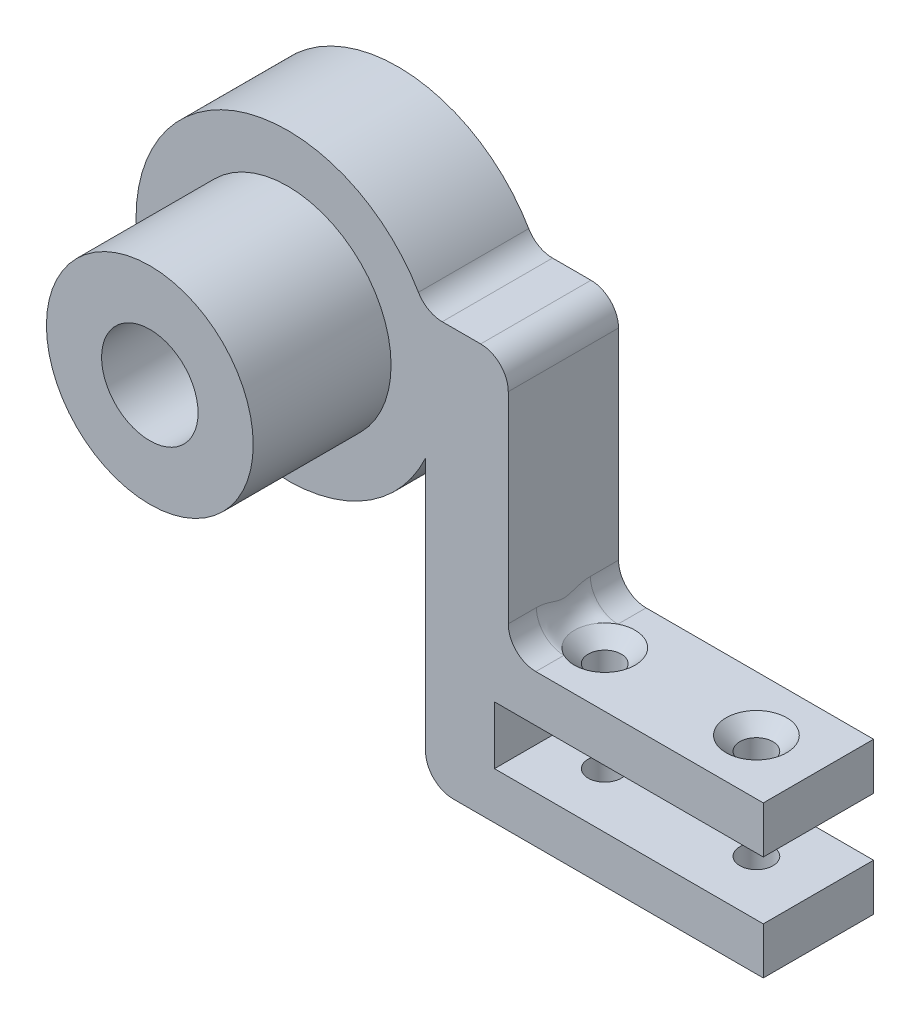
SolidWorks part; units mm, degrees
ref_plane "Plan de face" through (0, 0, 0) normal (0, 0, 1) x (1, 0, 0)
ref_plane "Plan de dessus" through (0, 0, 0) normal (0, 1, 0) x (1, 0, 0)
ref_plane "Plan de droite" through (0, 0, 0) normal (1, 0, 0) x (0, 0, -1)
sketch "Esquisse1" plane through (0, 0, 0) normal (0, 0, 1) x (1, 0, 0)
  line L1 (0, 0) -> (45.5, 0) construction
  line L2 (0, 0) -> (0, -36) construction
  line L3 (0, -36) -> (45.5, -36) construction
  line L4 (45.5, 0) -> (45.5, -36) construction
  line L5 (21, -6.4174) -> (27, -6.4174)
  line L7 (27, -6.4174) -> (27, -25)
  line L8 (45.5, -28.4) -> (45.5, -25)
  line L9 (45.5, -36) -> (21, -36)
  line L10 (45.5, -36) -> (45.5, -32.6)
  line L11 (45.5, -25) -> (27, -25)
  line L14 (21, -36) -> (21, -15.5826)
  line L17 (45.5, -32.6) -> (26, -32.6)
  line L19 (45.5, -28.4) -> (26, -28.4)
  line L20 (26, -32.6) -> (26, -28.4)
  line L21 (21, -6.4174) -> (21, -15.5826) construction
  arc A0 (21, -6.4174) -> (21, -15.5826) centre (11, -11) ccw
  point P6 (21, -11)
  point P20 (26, -30.5)
  dimension "D3" = 22
  dimension "D1" = 45.5
  dimension "D2" = 36
  dimension "D4" = 11
  dimension "D5" = 11
  dimension "D6" = 11
  dimension "D8" = 19.5
  dimension "D9" = 4.2
  dimension "D10" = 5.5
  dimension "D11" = 18.5
  dimension "D7" = 21
extrude "Boss.-Extru.1" add sketch "Esquisse1" along normal blind 8
sketch "Esquisse2" plane through (0, -25, 0) normal (0, 1, 0) x (1, 0, 0)
  line L0 (27, -8) -> (27, 0) construction
  line L1 (45.5, -8) -> (27, -8) construction
  circle A0 centre (30, -4) radius 1
  dimension "D1" = 2
  dimension "D2" = 3
  dimension "D3" = 4
extrude "Enlèv. mat.-Extru.1" cut sketch "Esquisse2" against normal up to surface (11 mm away) up to face at (33.25, -36, 4)
hole_wizard "Fraisage pour vis à tête fraisée M21" positions "Esquisse3" profile "Esquisse4" countersink size "M2" standard "ISO"
sketch "Esquisse3" plane through (0, -25, 0) normal (0, 1, 0) x (1, 0, 0)
  point P0 (30, -4)
sketch "Esquisse4" plane through (30, -25, 4) normal (1, 0, 0) x (0, 0, 1)
  line L0 (0, 0) -> (0, 11.721)
  line L1 (0, 11.721) -> (1.2, 11)
  line L2 (1.2, 11) -> (1.2, 1)
  line L3 (1.2, 1) -> (2.2, 0)
  line L5 (2.2, 0) -> (0, 0)
  line L6 (-1.2, 1) -> (-2.2, 0) construction
  line L10 (0, 11.721) -> (-1.2, 11) construction
  line L11 (0, -6.35) -> (0, 107.95) construction
  dimension "Diamètre du perçage" = 2.4
  dimension "Profondeur du perçage" = 11
  dimension "Diamètre du fraisage entrant" = 4.4
  dimension "Angle du fraisage entrant" = 90
  dimension "Angle de pointe" = 118
fillet "Congé1" radius 2 3 edges at (21, -36, 4) (21, -6.4174, 4) (27, -6.4174, 4)
sketch "Esquisse5" plane through (0, 0, 8) normal (0, 0, 1) x (1, 0, 0)
  circle A0 centre (11, -11) radius 7.5
  dimension "D1" = 15
extrude "Boss.-Extru.2" add sketch "Esquisse5" along normal blind 10
sketch "Esquisse6" plane through (0, 0, 0) normal (0, 0, -1) x (-1, 0, 0)
  line L0 (-11, -3.5) -> (-11, -18.5) construction
  line L1 (0, -4.0566) -> (0, -19.2348) construction
  line L2 (-19.6078, 0) -> (-3.8534, 0) construction
  circle A0 centre (-11, -3.5) radius 1
  circle A1 centre (-11, -18.5) radius 1
  arc A2 (-21, -15.5826) -> (-20.4856, -5.4301) centre (-11, -11) ccw construction
  circle A3 centre (-11, -11) radius 3.5 construction
  point P8 (-11, -11)
  dimension "D2" = 2
  dimension "D3" = 2
  dimension "D5" = 7
  dimension "D1" = 11
  dimension "D4" = 11
  dimension "D6" = 15
extrude "Enlèv. mat.-Extru.2" cut sketch "Esquisse6" against normal offset from surface (6 mm away) 2 up to face at (18.5, -11, 8)
sketch "Esquisse8" plane through (0, 0, 0) normal (0, 0, -1) x (-1, 0, 0)
  circle A0 centre (-11, -11) radius 3.5
  dimension "D1" = 7
extrude "Enlèv. mat.-Extru.3" cut sketch "Esquisse8" against normal up to surface (18 mm away) up to face at (18.5, -11, 18)
sketch "Esquisse9" plane through (0, -25, 0) normal (0, 1, 0) x (1, 0, 0)
  line L0 (45.5, -8) -> (27, -8) construction
  line L1 (45.5, -8) -> (45.5, 0) construction
  circle A0 centre (41, -4) radius 1
  dimension "D3" = 2
  dimension "D1" = 4
  dimension "D2" = 4.5
extrude "Enlèv. mat.-Extru.4" cut sketch "Esquisse9" against normal up to surface (11 mm away) up to face at (34.25, -36, 4)
hole_wizard "Fraisage pour vis à tête fraisée M22" positions "Esquisse10" profile "Esquisse11" countersink size "M2" standard "ISO"
sketch "Esquisse10" plane through (0, -25, 0) normal (0, 1, 0) x (1, 0, 0)
  point P0 (41, -4)
sketch "Esquisse11" plane through (41, -25, 4) normal (1, 0, 0) x (0, 0, 1)
  line L0 (0, 0) -> (0, 11.721)
  line L1 (0, 11.721) -> (1.2, 11)
  line L2 (1.2, 11) -> (1.2, 1)
  line L3 (1.2, 1) -> (2.2, 0)
  line L5 (2.2, 0) -> (0, 0)
  line L6 (-1.2, 1) -> (-2.2, 0) construction
  line L10 (0, 11.721) -> (-1.2, 11) construction
  line L11 (0, -6.35) -> (0, 107.95) construction
  dimension "Diamètre du perçage" = 2.4
  dimension "Profondeur du perçage" = 11
  dimension "Diamètre du fraisage entrant" = 4.4
  dimension "Angle du fraisage entrant" = 90
  dimension "Angle de pointe" = 118
fillet "Congé2" radius 2 1 edges at (27, -25, 4)
equation "\"D4@Esquisse1\"=\"D3@Esquisse1\"/2"
equation "\"D5@Esquisse1\"=\"D3@Esquisse1\"/2"
equation "\"D10@Esquisse1\"=\"D6@Esquisse1\"/2"
